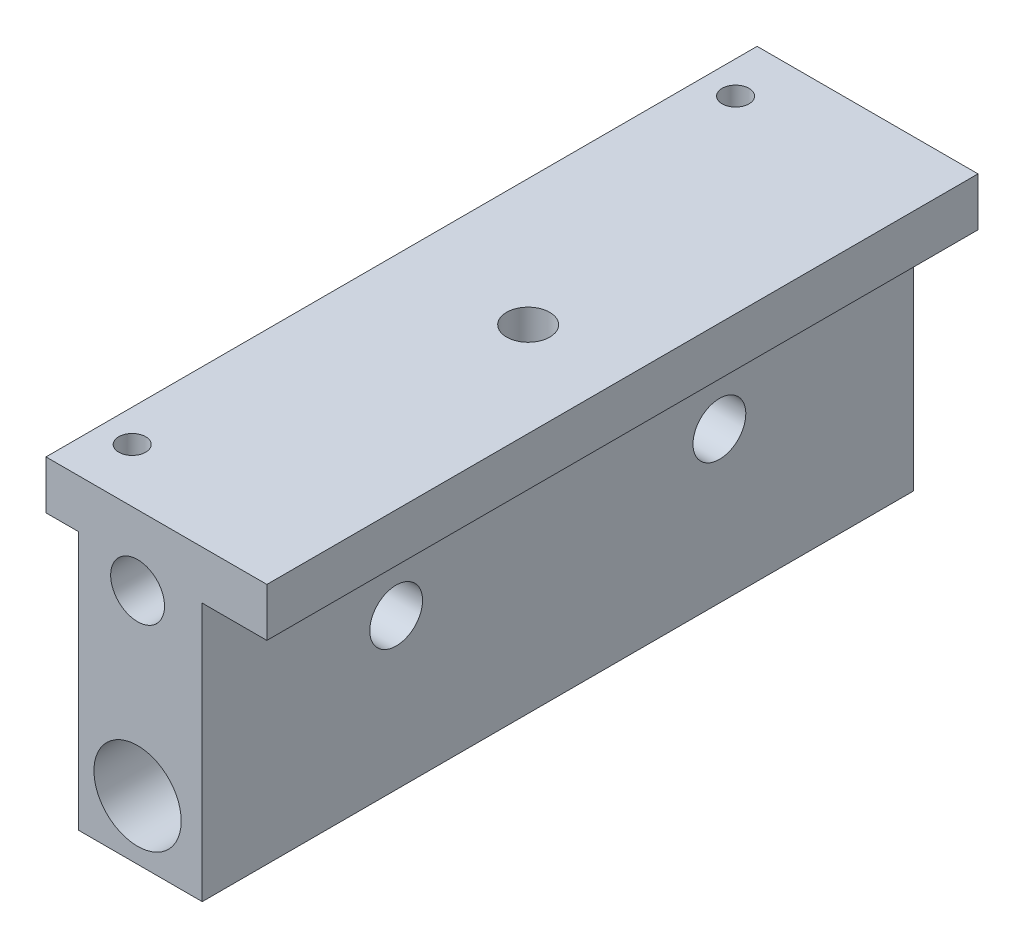
SolidWorks part; units mm, degrees
ref_plane "Front Plane" through (0, 0, 0) normal (0, 0, 1) x (1, 0, 0)
ref_plane "Top Plane" through (0, 0, 0) normal (0, 1, 0) x (1, 0, 0)
ref_plane "Right Plane" through (0, 0, 0) normal (1, 0, 0) x (0, 0, -1)
sketch "Sketch1" plane through (0, 0, 0) normal (0, 0, 1) x (1, 0, 0)
  line L0 (-4.1917, -22.0679) -> (-4.1917, 1.9321)
  line L1 (-4.1917, 1.9321) -> (-7.1917, 1.9321)
  line L2 (-7.1917, 1.9321) -> (-7.1917, 6.4321)
  line L3 (-7.1917, 6.4321) -> (13.3083, 6.4321)
  line L4 (13.3083, 6.4321) -> (13.3083, 1.9321)
  line L5 (13.3083, 1.9321) -> (7.3083, 1.9321)
  line L6 (7.3083, 1.9321) -> (7.3083, -22.0679)
  line L7 (7.3083, -22.0679) -> (-4.1917, -22.0679)
  circle A0 centre (1.3083, -16.5679) radius 4.05
  dimension "D6" = 8.1
  dimension "D1" = 20.5
  dimension "D2" = 3
  dimension "D3" = 28.5
  dimension "D4" = 24
  dimension "D5" = 11.5
  dimension "D7" = 5.5
  dimension "D8" = 8.5
extrude "Boss-Extrude1" add sketch "Sketch1" along normal blind 66
hole_wizard "M6x1.0 Tapped Hole1" positions "Sketch2" profile "Sketch3" tap size "M6x1.0" standard "ANSI Metric"
sketch "Sketch2" plane through (0, 0, 66) normal (0, 0, 1) x (1, 0, 0)
  line L0 (-7.1917, 6.4321) -> (-7.1917, 1.9321) construction
  line L1 (-4.1917, -22.0679) -> (7.3083, -22.0679) construction
  point P0 (1.3083, -0.0679)
  dimension "D1" = 8.5
  dimension "D2" = 22
sketch "Sketch3" plane through (1.3083, -0.0679, 66) normal (1, 0, 0) x (0, -1, 0)
  line L0 (0, 0) -> (0, 9.5022)
  line L1 (0, 9.5022) -> (2.5, 8)
  line L2 (2.5, 8) -> (2.5, 0)
  line L5 (2.5, 0) -> (0, 0)
  line L10 (0, 9.5022) -> (-2.5, 8) construction
  line L11 (0, -6.35) -> (0, 107.95) construction
  dimension "Tap Drill Dia." = 5
  dimension "Tap Drill Depth" = 8
  dimension "Drill Angle" = 118
cosmetic thread "Hole Thread1" parameters "D1"=8, "D2"=6
sketch "Sketch4" plane through (-4.1917, 0, 0) normal (-1, 0, 0) x (0, 0, 1)
  line L0 (66, -22.0679) -> (0, -22.0679) construction
  line L1 (0, 1.9321) -> (0, -22.0679) construction
  circle A0 centre (18, -8.0679) radius 4
  circle A1 centre (48, -8.0679) radius 4
  dimension "D1" = 8
  dimension "D2" = 14
  dimension "D3" = 18
  dimension "D4" = 48
extrude "Cut-Extrude1" cut sketch "Sketch4" against normal blind 7
sketch "Sketch5" plane through (2.8083, 0, 0) normal (-1, 0, 0) x (0, 0, 1)
  circle A0 centre (18, -8.0679) radius 2.45
  circle A1 centre (48, -8.0679) radius 2.45
  dimension "D1" = 4.9
extrude "Cut-Extrude2" cut sketch "Sketch5" against normal through all
hole_wizard "M4x0.7 Tapped Hole1" positions "Sketch6" profile "Sketch7" tap size "M4x0.7" standard "ANSI Metric"
sketch "Sketch6" plane through (-4.1917, 0, 0) normal (-1, 0, 0) x (0, 0, 1)
  line L0 (0, 1.9321) -> (0, -22.0679) construction
  point P0 (8, -8.3949)
  point P2 (58, -8.3949)
  dimension "D1" = 8
  dimension "D2" = 50
sketch "Sketch7" plane through (-4.1917, -8.3949, 8) normal (0, 1, 0) x (0, 0, 1)
  line L0 (0, 0) -> (0, 8.9914)
  line L1 (0, 8.9914) -> (1.65, 8)
  line L2 (1.65, 8) -> (1.65, 0)
  line L5 (1.65, 0) -> (0, 0)
  line L10 (0, 8.9914) -> (-1.65, 8) construction
  line L11 (0, -6.35) -> (0, 107.95) construction
  dimension "Tap Drill Dia." = 3.3
  dimension "Tap Drill Depth" = 8
  dimension "Drill Angle" = 118
cosmetic thread "Hole Thread2" parameters "D1"=8, "D2"=4
cosmetic thread "Hole Thread3" parameters "D1"=8, "D2"=4
sketch "Sketch8" plane through (0, 6.4321, 0) normal (0, 1, 0) x (1, 0, 0)
  line L0 (13.3083, 0) -> (-7.1917, 0) construction
  line L1 (13.3083, -66) -> (13.3083, 0) construction
  circle A0 centre (4.5583, -33) radius 2
  dimension "D1" = 4
  dimension "D2" = 33
  dimension "D3" = 8.75
extrude "Cut-Extrude3" cut sketch "Sketch8" against normal blind 15
hole_wizard "M3x0.5 Tapped Hole1" positions "Sketch10" profile "Sketch11" tap size "M3x0.5" standard "ANSI Metric"
sketch "Sketch10" plane through (0, -8.5679, 0) normal (0, 1, 0) x (1, 0, 0)
  circle A0 centre (4.5583, -33) radius 2 construction
  point P0 (4.5583, -33)
sketch "Sketch11" plane through (4.5583, -8.5679, 33) normal (1, 0, 0) x (0, 0, 1)
  line L0 (0, 0) -> (0, 5.7511)
  line L1 (0, 5.7511) -> (1.25, 5)
  line L2 (1.25, 5) -> (1.25, 0)
  line L5 (1.25, 0) -> (0, 0)
  line L10 (0, 5.7511) -> (-1.25, 5) construction
  line L11 (0, -6.35) -> (0, 107.95) construction
  dimension "Tap Drill Dia." = 2.5
  dimension "Tap Drill Depth" = 5
  dimension "Drill Angle" = 118
cosmetic thread "Hole Thread4" parameters "D1"=5, "D2"=3
hole_wizard "M3 Tapped Hole1" positions "Sketch12" profile "Sketch13" tap size "M3" standard "ISO"
sketch "Sketch12" plane through (0, 6.4321, 0) normal (0, 1, 0) x (1, 0, 0)
  line L0 (13.3083, 0) -> (-7.1917, 0) construction
  line L1 (-7.1917, -66) -> (-7.1917, 0) construction
  point P0 (-4.1917, -5)
  point P2 (-4.1917, -61)
  dimension "D1" = 5
  dimension "D2" = 5
  dimension "D3" = 3
  dimension "D4" = 3
sketch "Sketch13" plane through (-4.1917, 6.4321, 5) normal (1, 0, 0) x (0, 0, 1)
  line L0 (0, 0) -> (0, 8.2511)
  line L1 (0, 8.2511) -> (1.25, 7.5)
  line L2 (1.25, 7.5) -> (1.25, 0)
  line L5 (1.25, 0) -> (0, 0)
  line L10 (0, 8.2511) -> (-1.25, 7.5) construction
  line L11 (0, -6.35) -> (0, 107.95) construction
  dimension "Tap Drill Dia." = 2.5
  dimension "Tap Drill Depth" = 7.5
  dimension "Drill Angle" = 118
cosmetic thread "Hole Thread5" parameters "D1"=6, "D2"=3
cosmetic thread "Hole Thread6" parameters "D1"=6, "D2"=3
sketch "Sketch14" plane through (0, 0, 66) normal (0, 0, 1) x (1, 0, 0)
  circle A0 centre (1.3083, -0.0679) radius 2
  dimension "D1" = 4
sketch "Sketch15" plane through (0, 0, 0) normal (0, 0, -1) x (-1, 0, 0)
  circle A0 centre (-1.3083, -0.0679) radius 2
extrude "Cut-Extrude5" cut sketch "Sketch15" against normal blind 11
extrude "Cut-Extrude6" cut sketch "Sketch14" against normal blind 11
hole_wizard "M6 Tapped Hole2" positions "Sketch18" profile "Sketch19" tap size "M6" standard "ISO"
sketch "Sketch18" plane through (0, 0, 0) normal (0, 0, -1) x (-1, 0, 0)
  circle A0 centre (-1.3083, -0.0679) radius 2 construction
  point P0 (-1.3083, -0.0679)
sketch "Sketch19" plane through (1.3083, -0.0679, 0) normal (1, 0, 0) x (0, 1, 0)
  line L0 (0, 0) -> (0, 9.5022)
  line L1 (0, 9.5022) -> (2.5, 8)
  line L2 (2.5, 8) -> (2.5, 0)
  line L5 (2.5, 0) -> (0, 0)
  line L10 (0, 9.5022) -> (-2.5, 8) construction
  line L11 (0, -6.35) -> (0, 107.95) construction
  dimension "Tap Drill Dia." = 5
  dimension "Tap Drill Depth" = 8
  dimension "Drill Angle" = 118
cosmetic thread "Hole Thread7"
